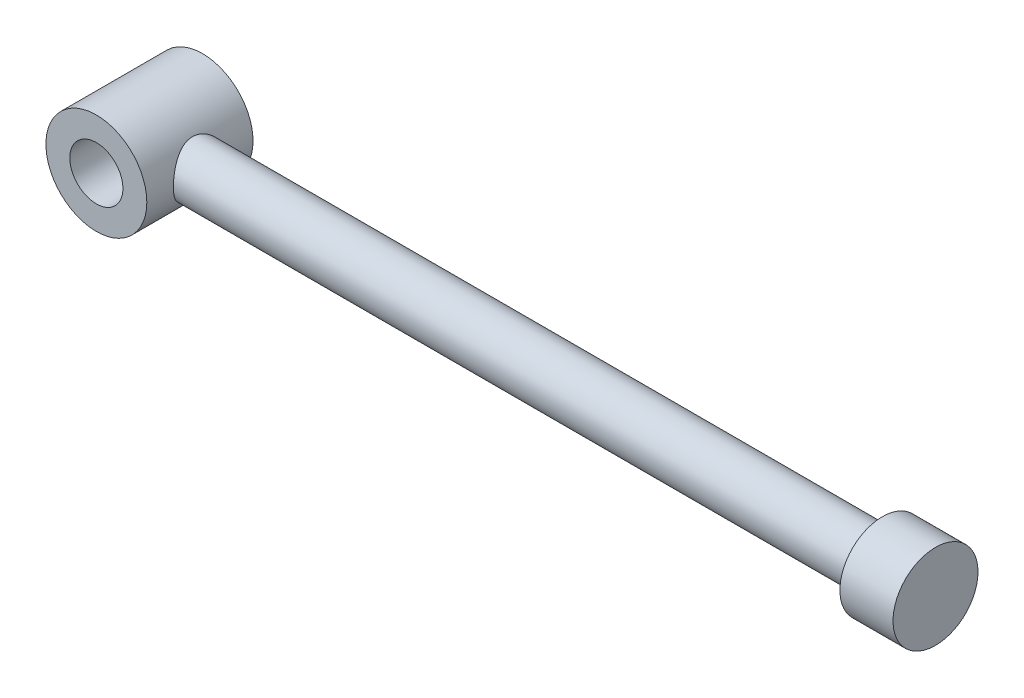
SolidWorks part; units mm, degrees
ref_plane "Front Plane" through (0, 0, 0) normal (0, 0, 1) x (1, 0, 0)
ref_plane "Top Plane" through (0, 0, 0) normal (0, 1, 0) x (1, 0, 0)
ref_plane "Right Plane" through (0, 0, 0) normal (1, 0, 0) x (0, 0, -1)
other "Configuration Table"
sketch "Sketch1" plane through (0, 0, 0) normal (0, 0, 1) x (1, 0, 0)
  circle A0 centre (0, 0) radius 25
  circle A1 centre (0, 0) radius 47.5
  dimension "D1" = 50
  dimension "D2" = 95
extrude "Boss-Extrude1" add sketch "Sketch1" along normal blind 100
ref_plane "Plane1" through (740, 0, 0) normal (1, 0, 0) x (0, 0, -1)
sketch "Sketch2" plane through (740, 0, 0) normal (1, 0, 0) x (0, 0, -1)
  line L0 (-100, 47.5) -> (-100, -47.5) construction
  circle A0 centre (-50, 0) radius 25
  dimension "D2" = 50
  dimension "D1" = 50
extrude "Boss-Extrude2" add sketch "Sketch2" against normal up to surface (692.5 mm away) up to face at (47.5, 0, 100)
sketch "Sketch3" plane through (740, 0, 0) normal (1, 0, 0) x (0, 0, -1)
  circle A0 centre (-50, 0) radius 40
  dimension "D1" = 80
extrude "Boss-Extrude3" add sketch "Sketch3" against normal blind 50
ref_point "Point1"
ref_axis "Axis1" through (38.6768, 0, 50) along (1, 0, 0)
ref_point "Point2"
ref_axis "Axis2" through (0, 0, 100) along (0, 0, -1)
ref_plane "Plane2" through (0, 0, 0) normal (0, -1, 0) x (1, 0, 0)
